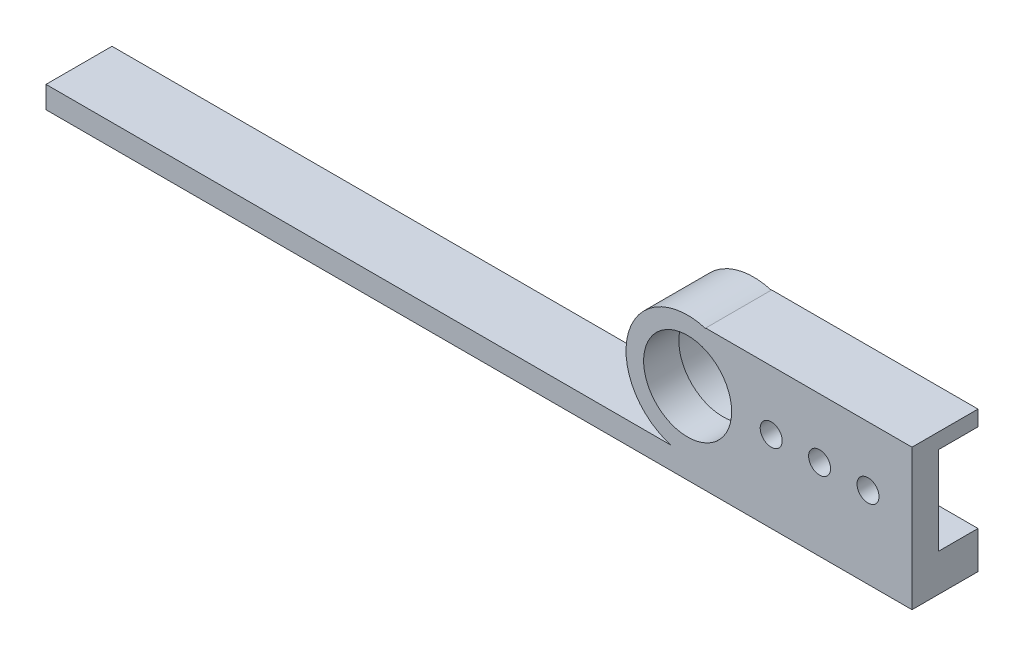
SolidWorks part; units mm, degrees
ref_plane "前视基准面" through (0, 0, 0) normal (0, 0, 1) x (1, 0, 0)
ref_plane "上视基准面" through (0, 0, 0) normal (0, 1, 0) x (1, 0, 0)
ref_plane "右视基准面" through (0, 0, 0) normal (1, 0, 0) x (0, 0, -1)
sketch "草图1" plane through (0, 0, 0) normal (0, 0, 1) x (1, 0, 0)
  line L1 (20, -10) -> (-20, -10)
  line L2 (20, -10) -> (20, 10)
  line L3 (20, 10) -> (-20, 10)
  line L4 (-20, -10) -> (-20, 10)
  line L5 (20, -10) -> (-20, 10) construction
  line L6 (20, 10) -> (-20, -10) construction
  point P0 (0, 0)
  dimension "D1" = 40
  dimension "D2" = 20
extrude "凸台-拉伸1" add sketch "草图1" along normal blind 6
sketch "草图2" plane through (0, 0, 6) normal (0, 0, 1) x (1, 0, 0)
  line L0 (20, -10) -> (20, 10) construction
  circle A0 centre (10, 0) radius 2.5
  circle A1 centre (-1, 0) radius 2.5
  circle A2 centre (-12, 0) radius 2.5
  dimension "D1" = 10
  dimension "D2" = 5
  dimension "D3" = 3
extrude "切除-拉伸1" cut sketch "草图2" against normal through all
sketch "草图3" plane through (0, 0, 6) normal (0, 0, 1) x (1, 0, 0)
  line L0 (20, 13.5) -> (20, 10)
  line L1 (20, -13.5) -> (-26.894, -13.5)
  line L3 (20, 13.5) -> (-26.894, 13.5)
  line L4 (-20, 10) -> (-20, -10)
  line L5 (-20, -10) -> (20, -10)
  line L6 (20, -10) -> (20, 10)
  line L7 (20, 10) -> (-20, 10)
  line L8 (-20, 10) -> (-20, -10)
  line L9 (-20, -10) -> (20, -10)
  line L10 (20, -10) -> (20, 10)
  line L11 (20, 10) -> (-20, 10)
  line L12 (-26.894, -13.5) -> (-26.894, 13.5)
  line L13 (20, -10.0394) -> (-26.894, 13.5) construction
  line L14 (20, 10.0394) -> (-26.894, -13.5) construction
  line L15 (20, -10) -> (20, -13.5)
  circle A0 centre (-31, 0) radius 11
  circle A1 centre (-31, 0) radius 14
  point P2 (0, 0)
  line M10 (-20, 10) -> (-20, -10)
  line M11 (-20, -10) -> (20, -10)
  line M13 (20, 10) -> (-20, 10)
  dimension "D3" = 22
  dimension "D4" = 28
  dimension "D2" = 3.5
  dimension "D1" = 0
extrude "凸台-拉伸2" add sketch "草图3" against normal blind 15 contours L3 A1 L1 L12 A0 | A1 L1 L15 M11 M10 | L1 A1 L8 A0 L12 | L8 A1 L3 L12 A0 | L8 A1 | A1 L0 L3 M10 M13 region at (-1.9449, 11.7771, 6) region at (-1.9449, -11.7771, 6) region at (-23.0173, 9.0328, 6) region at (-27.2274, 11.7946, 6) region at (-18.7882, 0, 6) region at (-23.0173, -9.0328, 6)
sketch "草图5" plane through (0, 0, 6) normal (0, 0, 1) x (1, 0, 0)
  circle A0 centre (-31, 0) radius 10
  circle A1 centre (-31, 0) radius 11 construction
  circle A2 centre (-31, 0) radius 11
  dimension "D1" = 20
extrude "凸台-拉伸3" add sketch "草图5" against normal blind 8
sketch "草图6" plane through (0, 0, 6) normal (0, 0, 1) x (1, 0, 0)
  circle A0 centre (-31, 0) radius 8.5
  circle A1 centre (-31, 0) radius 10 construction
  circle A2 centre (-31, 0) radius 10
  dimension "D1" = 17
sketch "草图9" plane through (0, -13.5, 0) normal (0, -1, 0) x (1, 0, 0)
  circle A0 centre (-18.2368, -1.344) radius 5.5352
sketch "草图10" plane through (20, 0, 0) normal (1, 0, 0) x (0, 0, -1)
  line L1 (9, -13.5) -> (-6, -13.5)
  line L2 (9, -13.5) -> (9, -18.5)
  line L3 (9, -18.5) -> (-6, -18.5)
  line L4 (-6, -13.5) -> (-6, -18.5)
  dimension "D1" = 5
extrude "凸台-拉伸4" add sketch "草图10" against normal blind 200
sketch "草图11" plane through (0, 0, 6) normal (0, 0, 1) x (1, 0, 0)
  line L1 (-28.6193, -11.8661) -> (-25.5243, -11.8661)
  line L2 (-28.6193, -11.8661) -> (-28.6193, -14.961)
  line L3 (-28.6193, -14.961) -> (-25.5243, -14.961)
  line L4 (-25.5243, -11.8661) -> (-25.5243, -14.961)
extrude "凸台-拉伸5" add sketch "草图11" against normal through all
sketch "草图13" plane through (0, -18.5, 0) normal (0, -1, 0) x (1, 0, 0)
  line L0 (-176.8267, 6) -> (-176.8267, -9)
  line L1 (-180, 6) -> (20, 6) construction
  line L2 (-176.8267, 19.5002) -> (-176.8267, -350.4998) construction
  line L3 (-180, -9) -> (20, -9) construction
sketch "草图14" plane through (0, -18.5, 0) normal (0, -1, 0) x (1, 0, 0)
  line L0 (-118.4338, -15.7251) -> (-118.4338, 9.3691)
  line L1 (-118.4338, 126.7017) -> (-118.4338, -243.2983) construction
sketch "草图15" plane through (0, -18.5, 0) normal (0, -1, 0) x (1, 0, 0)
  line L1 (-118.4338, -15.7251) -> (-184.1416, -15.7251)
  line L2 (-118.4338, -15.7251) -> (-118.4338, 11.9644)
  line L3 (-118.4338, 11.9644) -> (-184.1416, 11.9644)
  line L4 (-184.1416, -15.7251) -> (-184.1416, 11.9644)
sketch "草图16" plane through (0, -18.5, 0) normal (0, -1, 0) x (1, 0, 0)
  line L0 (-176.8267, 6.4407) -> (-176.8267, -38.9947)
  line L1 (-176.8267, 19.5002) -> (-176.8267, -350.4998) construction
sketch "草图17" plane through (0, -18.5, 0) normal (0, -1, 0) x (1, 0, 0)
  line L0 (-176.8267, 7.3332) -> (-176.8267, -35.3686)
  line L1 (-176.8267, 19.5002) -> (-176.8267, -350.4998) construction
sketch "草图18" plane through (0, -18.5, 0) normal (0, -1, 0) x (1, 0, 0)
  line L1 (-176.8267, -38.9947) -> (-206.846, -38.9947)
  line L2 (-176.8267, -38.9947) -> (-176.8267, 25.1925)
  line L3 (-176.8267, 25.1925) -> (-206.846, 25.1925)
  line L4 (-206.846, -38.9947) -> (-206.846, 25.1925)
extrude "切除-拉伸3" cut sketch "草图18" against normal through all
